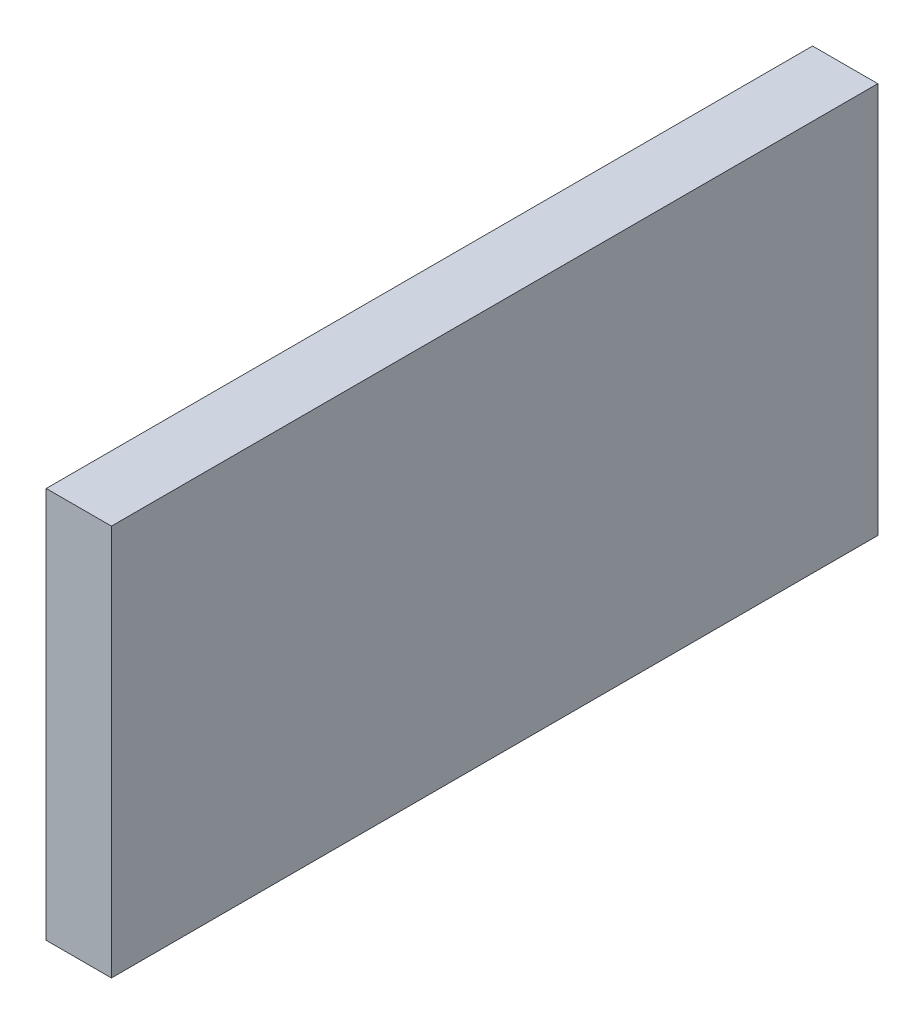
SolidWorks part; units mm, degrees
material "Acrylic (Medium-high impact)"
ref_plane "Front Plane" through (0, 0, 0) normal (0, 0, 1) x (1, 0, 0)
ref_plane "Top Plane" through (0, 0, 0) normal (0, 1, 0) x (1, 0, 0)
ref_plane "Right Plane" through (0, 0, 0) normal (1, 0, 0) x (0, 0, -1)
sketch "Sketch1" plane through (0, 0, 74.5305) normal (0, 0, -1) x (-1, 0, 0)
  line L0 (-51.9215, 29.1718) -> (-56.9215, 29.1718) construction
  line L1 (-56.9215, 47.1718) -> (-53.9215, 47.1718)
  line L2 (-56.9215, 47.1718) -> (-56.9215, 29.1718)
  line L3 (-56.9215, 29.1718) -> (-53.9215, 29.1718)
  line L4 (-53.9215, 47.1718) -> (-53.9215, 29.1718)
  dimension "D1" = 3
extrude "Boss-Extrude1" add sketch "Sketch1" along normal up to surface (35.25 mm away)
